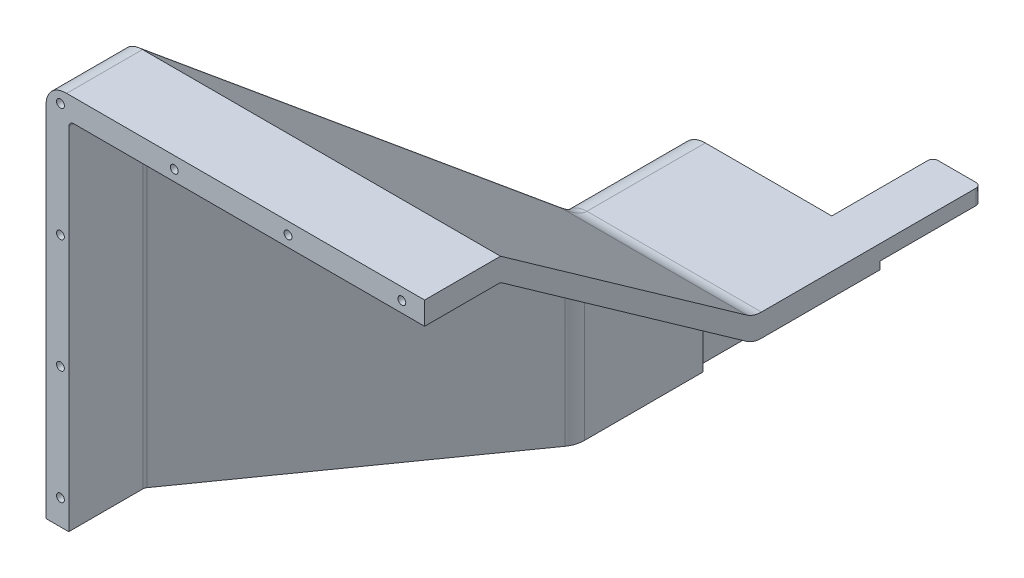
SolidWorks part; units mm, degrees
ref_plane "前视基准面" through (0, 0, 0) normal (0, 0, 1) x (1, 0, 0)
ref_plane "上视基准面" through (0, 0, 0) normal (0, 1, 0) x (1, 0, 0)
ref_plane "右视基准面" through (0, 0, 0) normal (1, 0, 0) x (0, 0, -1)
other "Configuration Table"
sketch "草图1" plane through (0, 0, 0) normal (0, 0, 1) x (1, 0, 0)
  line L0 (0, 0) -> (0, 79)
  line L1 (0, 79) -> (79, 79)
  line L2 (79, 79) -> (79, 70)
  line L3 (79, 70) -> (9, 70)
  line L4 (9, 70) -> (9, 0)
  line L5 (9, 0) -> (0, 0)
  dimension "D1" = 9
  dimension "D2" = 9
  dimension "D3" = 70
  dimension "D4" = 70
ref_plane "基准面1" through (0, 0, 100) normal (0, 0, 1) x (1, 0, 0)
sketch "草图2" plane through (0, 0, 100) normal (0, 0, 1) x (1, 0, 0)
  line L0 (0, 79) -> (-70.7107, 149.7107) construction
  line L1 (0, 0) -> (0, 79) construction
  line L2 (-70.7107, 149.7107) -> (-70.7107, 0)
  line L3 (-70.7107, 0) -> (-61.7107, 0)
  line L4 (-61.7107, 0) -> (-61.7107, 140.7107)
  line L5 (-61.7107, 140.7107) -> (79, 140.7107)
  line L6 (79, 140.7107) -> (79, 149.7107)
  line L7 (79, 149.7107) -> (-70.7107, 149.7107)
  line L8 (0, 0) -> (0, 79) construction
  line L9 (0, 79) -> (79, 79) construction
  dimension "D1" = 135
  dimension "D2" = 9
  dimension "D3" = 100
  dimension "D4" = 79
loft "放样1" add profiles "草图1", "草图2" connector at (79, 79, 0) connector at (79, 149.2162, 100)
sketch "草图4" plane through (0, 0, 0) normal (0, 0, -1) x (-1, 0, 0)
  line L7 (-9, 0) -> (0, 0)
  line L8 (0, 0) -> (0, 79)
  line L9 (0, 79) -> (-79, 79)
  line L10 (-79, 79) -> (-79, 70)
  line L11 (-79, 70) -> (-77.7656, 70)
  line L12 (-77.7656, 70) -> (-9, 70)
  line L13 (-9, 70) -> (-9, 0)
  line L14 (-9, 0) -> (0, 0)
  line L15 (0, 0) -> (0, 79)
  line L16 (0, 79) -> (-79, 79)
  line L17 (-79, 79) -> (-79, 70)
  line L18 (-79, 70) -> (-77.7656, 70)
  line L19 (-77.7656, 70) -> (-9, 70)
  line L20 (-9, 70) -> (-9, 0)
  dimension "D1" = 0
extrude "凸台-拉伸1" add sketch "草图4" along normal blind 50
sketch "草图9" plane through (0, 0, -50) normal (0, 0, -1) x (-1, 0, 0)
  line L0 (-9, 70) -> (-9, 0) construction
  line L1 (-9, 70) -> (-55, 70)
  line L2 (-9, 70) -> (-9, 30)
  line L3 (-15, 64) -> (-55, 64)
  line L4 (-55, 70) -> (-55, 64)
  line L6 (-15, 64) -> (-15, 30)
  line L7 (-15, 30) -> (-9, 30)
  dimension "D1" = 6
  dimension "D2" = 46
  dimension "D3" = 6
  dimension "D4" = 40
extrude "凸台-拉伸3" add sketch "草图9" against normal blind 6
fillet "圆角1" radius 10 9 edges
sketch "草图11" plane through (0, 0, -44) normal (0, 0, 1) x (1, 0, 0)
  circle A0 centre (12, 45) radius 1.55
  circle A1 centre (12, 65) radius 1.55
  circle A2 centre (30, 67) radius 1.55
  circle A3 centre (50, 67) radius 1.55
  dimension "D1" = 3.1
extrude "切除-拉伸1" cut sketch "草图11" against normal through all
sketch "草图12" plane through (0, 0, -50) normal (0, 0, -1) x (-1, 0, 0)
  line L0 (0, 19) -> (0, 0)
  line L1 (0, 0) -> (0, 69) construction
  line L2 (0, 0) -> (-6, 0)
  line L3 (-9, 0) -> (0, 0) construction
  line L5 (-6, 0) -> (-6, 19)
  line L6 (0, 19) -> (-6, 19)
  line L7 (-2.9289, 76.0711) -> (-93.7798, -14.7798) construction
  line L8 (0, 0) -> (0, 69) construction
  line L9 (-60, 79) -> (-60, 73)
  line L10 (-79, 73) -> (-60, 73)
  line L11 (-79, 79) -> (-79, 73)
  line L12 (-60, 79) -> (-79, 79)
  arc A0 (0, 69) -> (-10, 79) centre (-10, 69) ccw construction
  dimension "D1" = 19
  dimension "D2" = 6
  dimension "D3" = 45
extrude "凸台-拉伸4" add sketch "草图12" along normal blind 40
fillet "圆角2" radius 2 9 edges at (3, 0, -90) (3, 19, -90) (9, 30, -47) (15, 30, -47) (15, 64, -47) (55, 70, -47) (55, 64, -47) (79, 76, -90) (60, 76, -90)
sketch "草图13" plane through (79, 0, 0) normal (1, 0, 0) x (0, 0, -1)
  line L0 (90, 79) -> (88, 79) construction
  line L1 (90, 79) -> (90, 73) construction
  line L9 (50, 73) -> (88, 73)
  line L10 (88, 73) -> (88, 79)
  line L11 (88, 79) -> (3.1784, 79)
  line L12 (-2.5951, 80.835) -> (-100, 149.7107)
  line L13 (-100, 149.7107) -> (-100, 149.2162)
  line L14 (-100, 149.2162) -> (-100, 140.7107)
  line L15 (-100, 140.7107) -> (-2.5951, 71.835)
  line L16 (3.1784, 70) -> (50, 70)
  line L17 (50, 70) -> (50, 73)
  line L18 (50, 73) -> (90, 73)
  line L19 (90, 73) -> (90, 79)
  line L20 (90, 79) -> (3.1784, 79)
  line L21 (-2.5951, 80.835) -> (-100, 149.7107)
  line L22 (-100, 149.7107) -> (-100, 149.2162)
  line L23 (-100, 149.2162) -> (-100, 140.7107)
  line L24 (-100, 140.7107) -> (-2.5951, 71.835)
  line L25 (3.1784, 70) -> (50, 70)
  line L26 (50, 70) -> (50, 73)
  arc A2 (-2.5951, 80.835) -> (3.1784, 79) centre (3.1784, 89) ccw
  arc A3 (-2.5951, 71.835) -> (3.1784, 70) centre (3.1784, 80) ccw
  arc A4 (-2.5951, 80.835) -> (3.1784, 79) centre (3.1784, 89) ccw
  arc A5 (-2.5951, 71.835) -> (3.1784, 70) centre (3.1784, 80) ccw
  dimension "D1" = 0
sketch "草图14" plane through (0, 0, 100) normal (0, 0, 1) x (1, 0, 0)
  line L8 (79, 149.7107) -> (-62.5457, 149.7107)
  line L9 (-70.7107, 141.5457) -> (-70.7107, 111.0839)
  line L10 (-70.7107, 111.0839) -> (-70.7107, 0)
  line L11 (-70.7107, 0) -> (-61.7107, 0)
  line L12 (-61.7107, 0) -> (-61.7107, 140.7107)
  line L13 (-61.7107, 140.7107) -> (79, 140.7107)
  line L14 (79, 140.7107) -> (79, 149.2162)
  line L15 (79, 149.2162) -> (79, 149.7107)
  line L16 (79, 149.7107) -> (-62.5457, 149.7107)
  line L17 (-70.7107, 141.5457) -> (-70.7107, 111.0839)
  line L18 (-70.7107, 111.0839) -> (-70.7107, 0)
  line L19 (-70.7107, 0) -> (-61.7107, 0)
  line L20 (-61.7107, 0) -> (-61.7107, 140.7107)
  line L21 (-61.7107, 140.7107) -> (79, 140.7107)
  line L22 (79, 140.7107) -> (79, 149.2162)
  line L23 (79, 149.2162) -> (79, 149.7107)
  ellipse E1 centre (-58.4632, 137.4632) end of major axis (-68.4632, 147.4632) minor radius 10 (-62.5457, 149.7107) -> (-70.7107, 141.5457) ccw
  ellipse E2 centre (-58.4632, 137.4632) end of major axis (-68.4632, 147.4632) minor radius 10 (-62.5457, 149.7107) -> (-70.7107, 141.5457) ccw
  dimension "D1" = 0
extrude "凸台-拉伸6" add sketch "草图14" along normal blind 30
sketch "草图15" plane through (0, 0, 130) normal (0, 0, 1) x (1, 0, 0)
  circle A0 centre (-65, 145) radius 1.55
  circle A1 centre (-20, 145) radius 1.55
  circle A2 centre (25, 145) radius 1.55
  circle A3 centre (70, 145) radius 1.55
  circle A4 centre (-65, 100) radius 1.55
  circle A5 centre (-65, 55) radius 1.55
  circle A6 centre (-65, 10) radius 1.55
  dimension "D1" = 3.1
  dimension "D2" = 145
  dimension "D3" = 65
  dimension "D5" = 45
  dimension "D7" = 45
  dimension "D4" = 4
  dimension "D6" = 4
extrude "切除-拉伸2" cut sketch "草图15" against normal blind 5
fillet "圆角3" radius 2 4 edges at (8.5302, 70.4698, -0.1493)
fillet "圆角4" radius 2 3 edges at (-61.1249, 140.1249, 99.8072)
